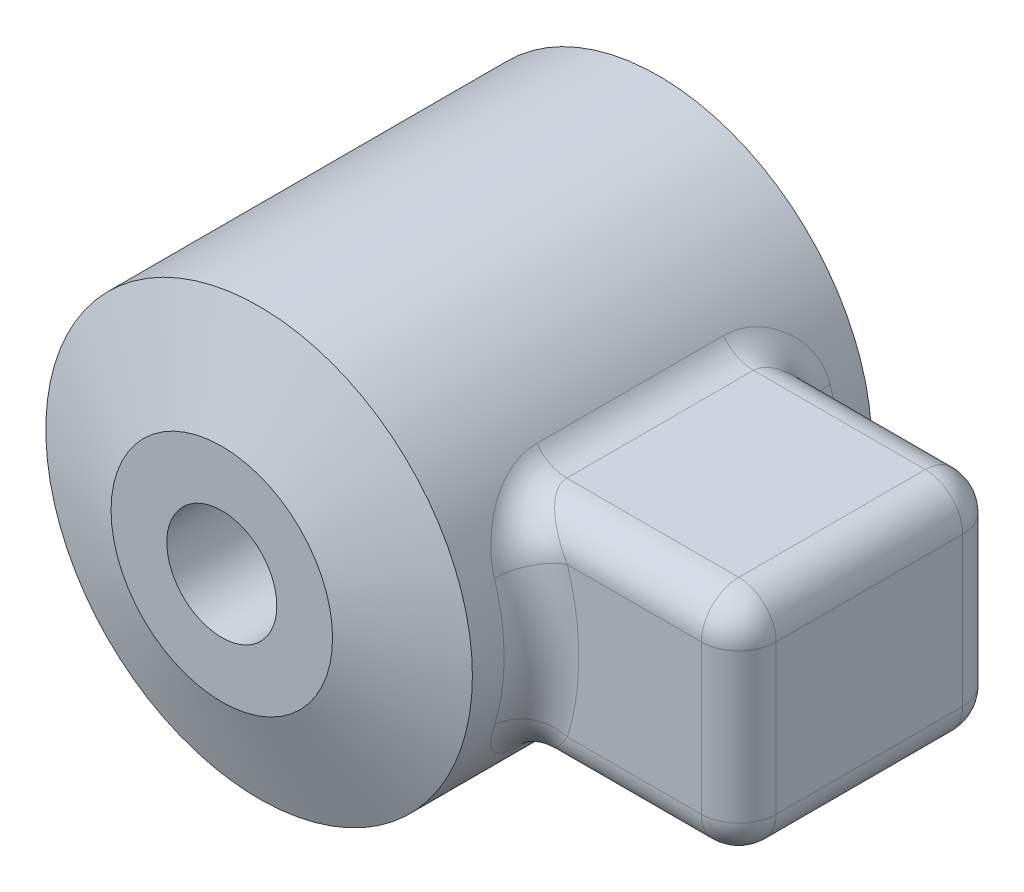
SolidWorks part; units mm, degrees
material "7075-T6 (SN)"
ref_plane "Front Plane" through (0, 0, 0) normal (0, 0, 1) x (1, 0, 0)
ref_plane "Top Plane" through (0, 0, 0) normal (0, 1, 0) x (1, 0, 0)
ref_plane "Right Plane" through (0, 0, 0) normal (1, 0, 0) x (0, 0, -1)
sketch "Sketch1" plane through (0, 0, 0) normal (0, 0, 1) x (1, 0, 0)
  circle A0 centre (0, 0) radius 5.715
  dimension "D1" = 11.43
extrude "Boss-Extrude1" add sketch "Sketch1" along normal blind 12.7
sketch "Sketch2" plane through (0, 0, 12.7) normal (0, 0, 1) x (1, 0, 0)
  circle A0 centre (0, 0) radius 1.4732
  dimension "D1" = 2.9464
extrude "Cut-Extrude1" cut sketch "Sketch2" against normal through all
chamfer "Chamfer1" distance 1 angle 70 1 edges at (5.715, 0, 12.7) first distance on face at (5.715, 0, 12.7)
chamfer "Chamfer3" distance 1 angle 70 1 edges at (5.715, 0, 0) first distance on face at (5.715, 0, 11.7)
ref_plane "Plane2" through (4, 0, 0) normal (1, 0, 0) x (0, 0, -1)
sketch "Sketch3" plane through (4, 0, 0) normal (1, 0, 0) x (0, 0, -1)
  line L0 (6.2865, 0) -> (-6.2865, 0) construction
  line L1 (-9.85, 3) -> (-2.85, 3)
  line L2 (-9.85, 3) -> (-9.85, -3)
  line L3 (-9.85, -3) -> (-2.85, -3)
  line L4 (-2.85, 3) -> (-2.85, -3)
  line L5 (-9.85, 3) -> (-2.85, -3) construction
  line L6 (-9.85, -3) -> (-2.85, 3) construction
  line L7 (0, 6.2865) -> (0, -6.2865) construction
  point P0 (-6.35, 0)
  dimension "D1" = 6.35
  dimension "D2" = 6
  dimension "D3" = 7
extrude "Boss-Extrude2" add sketch "Sketch3" along normal blind 7
fillet "Fillet1" radius 1 12 edges at (11, -3, 6.35) (11, 0, 9.85) (11, 3, 6.35) (11, 0, 2.85) (5.715, 0, 2.85) (4.8643, -3, 6.35) (5.715, 0, 9.85) (4.8643, 3, 6.35) (7.9321, -3, 2.85) (7.9321, -3, 9.85) (7.9321, 3, 2.85) (7.9321, 3, 9.85)
equation "\"FrangiboltTotalDiameter\"= 0.450in"
equation "\"FrangiboltTotalLength\"= 0.500in"
equation "\"FrangiboltThruHoleDiameter\"= 0.116in"
equation "\"D1@Sketch1\"=\"FrangiboltTotalDiameter\""
equation "\"D1@Boss-Extrude1\"=\"FrangiboltTotalLength\""
equation "\"D1@Sketch2\"=\"FrangiboltThruHoleDiameter\""
equation "\"D1@Sketch3\"=\"FrangiboltTotalLength\"/2"
